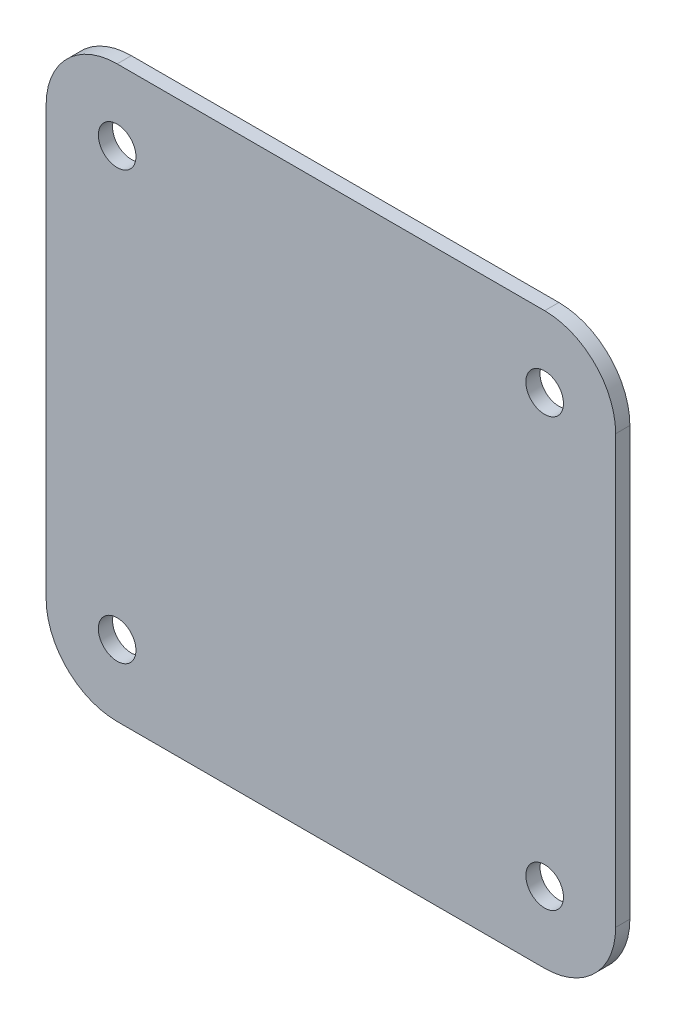
SolidWorks part; units mm, degrees
ref_plane "Front Plane" through (0, 0, 0) normal (0, 0, 1) x (1, 0, 0)
ref_plane "Top Plane" through (0, 0, 0) normal (0, 1, 0) x (1, 0, 0)
ref_plane "Right Plane" through (0, 0, 0) normal (1, 0, 0) x (0, 0, -1)
sketch "Sketch1" plane through (0, 0, 0) normal (0, 0, 1) x (1, 0, 0)
  line L0 (-30.1, 0) -> (30.1, 0) construction
  line L1 (-40.1, -40.1) -> (40.1, -40.1)
  line L2 (-40.1, -40.1) -> (-40.1, 40.1)
  line L3 (-40.1, 40.1) -> (40.1, 40.1)
  line L4 (40.1, -40.1) -> (40.1, 40.1)
  line L5 (-40.1, -40.1) -> (40.1, 40.1) construction
  line L6 (-40.1, 40.1) -> (40.1, -40.1) construction
  line L7 (55, 0) -> (-55, 0) construction
  line L8 (-30.1, -30.1) -> (-30.1, 30.1) construction
  line L9 (30.1, -30.1) -> (30.1, 30.1) construction
  point P0 (0, 0)
  point P11 (0, 0)
  point P14 (-30.1, 0)
  point P17 (30.1, 0)
  dimension "D1" = 60.2
  dimension "D2" = 10
  dimension "D3" = 10
extrude "Boss-Extrude1" add sketch "Sketch1" along normal blind 2 contours L2 L3 L4 L1
hole_wizard "M5 Clearance Hole1" positions "3DSketch1" profile "Sketch2" hole size "M5" standard "ANSI Metric" end condition through all
sketch3d "3DSketch1"
  point P0 (30.1, 30.1, 0)
  point P2 (-30.1, 30.1, 0)
  point P4 (-30.1, -30.1, 0)
  point P6 (30.1, -30.1, 0)
sketch "Sketch2" plane through (30.1, 30.1, 0) normal (1, 0, 0) x (0, 1, 0)
  line L0 (0, 0) -> (0, 2)
  line L1 (0, 2) -> (2.65, 2)
  line L2 (2.65, 2) -> (2.65, 0)
  line L5 (2.65, 0) -> (0, 0)
  line L11 (0, -6.35) -> (0, 107.95) construction
  dimension "Thru Hole Dia." = 5.3
  dimension "Thru Hole Depth" = 2
fillet "Fillet1" radius 10 4 edges at (-40.1, 40.1, 1) (-40.1, -40.1, 1) (40.1, -40.1, 1) (40.1, 40.1, 1)
